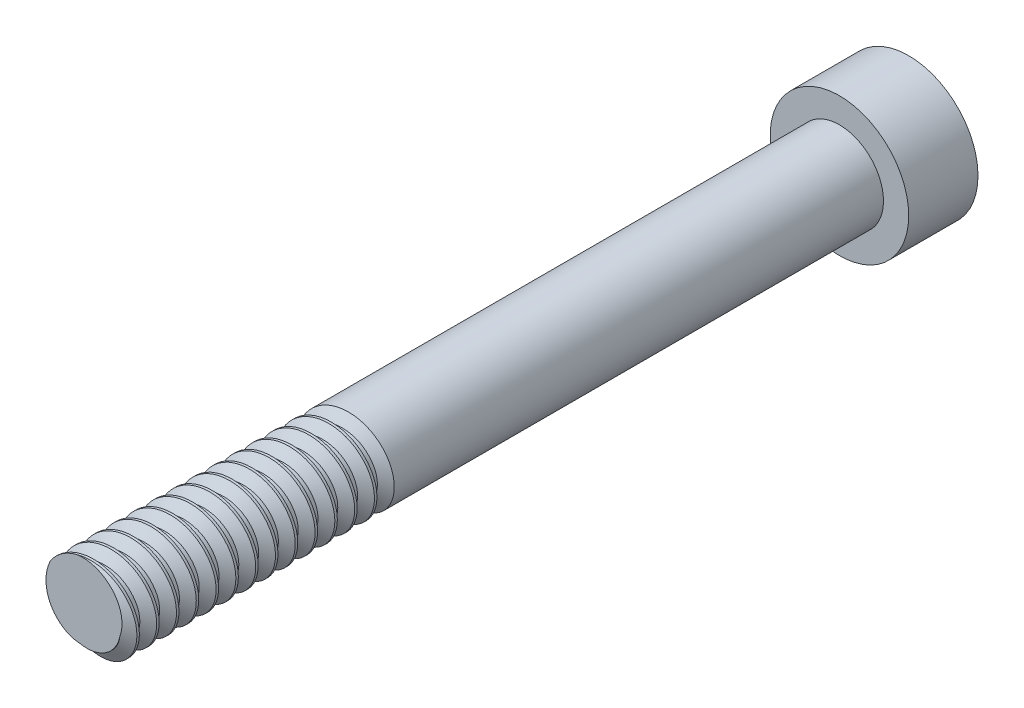
SolidWorks part; units mm, degrees
ref_plane "Front Plane" through (0, 0, 0) normal (0, 0, 1) x (1, 0, 0)
ref_plane "Top Plane" through (0, 0, 0) normal (0, 1, 0) x (1, 0, 0)
ref_plane "Right Plane" through (0, 0, 0) normal (1, 0, 0) x (0, 0, -1)
sketch "Sketch1" plane through (0, 0, 0) normal (0, 0, 1) x (1, 0, 0)
  circle A0 centre (0, 0) radius 3.5
  dimension "D1" = 7
extrude "Boss-Extrude1" add sketch "Sketch1" along normal blind 3.5
sketch "Sketch2" plane through (0, 0, 3.5) normal (0, 0, 1) x (1, 0, 0)
  circle A0 centre (0, 0) radius 2.225
  dimension "D1" = 4.45
extrude "Boss-Extrude2" add sketch "Sketch2" along normal blind 38
sketch "Sketch3" plane through (0, 0, 0) normal (0, 1, 0) x (1, 0, 0)
  line L0 (0, -43.5937) -> (0, -29.5)
  line L1 (0, -3.5) -> (0, -28.5) construction
  line L2 (-3.5, -3.5) -> (3.5, -3.5) construction
  point P7 (0, 0)
  point P8 (0, 0)
  point P9 (0, 0)
  point P10 (0, -43.5937)
  dimension "D1" = 25
  dimension "D2" = 1
thread "Thread1" pitch 1 method cut profile "Thread Profile2" start angle 0, offset 0, length 0, pitch 1, diameter 4.45
ref_plane "Plane2" through (-2.225, 0, 43.5937) normal (0, -1, 0) x (-1, 0, 0)
sketch "Thread Profile2" plane through (-2.225, 0, 43.5937) normal (0, -1, 0) x (-1, 0, 0)
  line L0 (0, 0) -> (0, 1) construction
  line L11 (0, 0) -> (0, 0.875)
  line L12 (0, 0.875) -> (-0.5413, 0.5625)
  line L13 (-0.5413, 0.5625) -> (-0.5413, 0.3125)
  line L15 (-0.5413, 0.3125) -> (0, 0)
  line L17 (-0.5413, 0.4375) -> (0, 0.4375) construction
  point P2 (0, 0)
  dimension "Pitch" = 1
  dimension "Profile_Angle" = 60
  dimension "Profile_Land" = 0.25
  dimension "Profile_Height" = 0.5413
